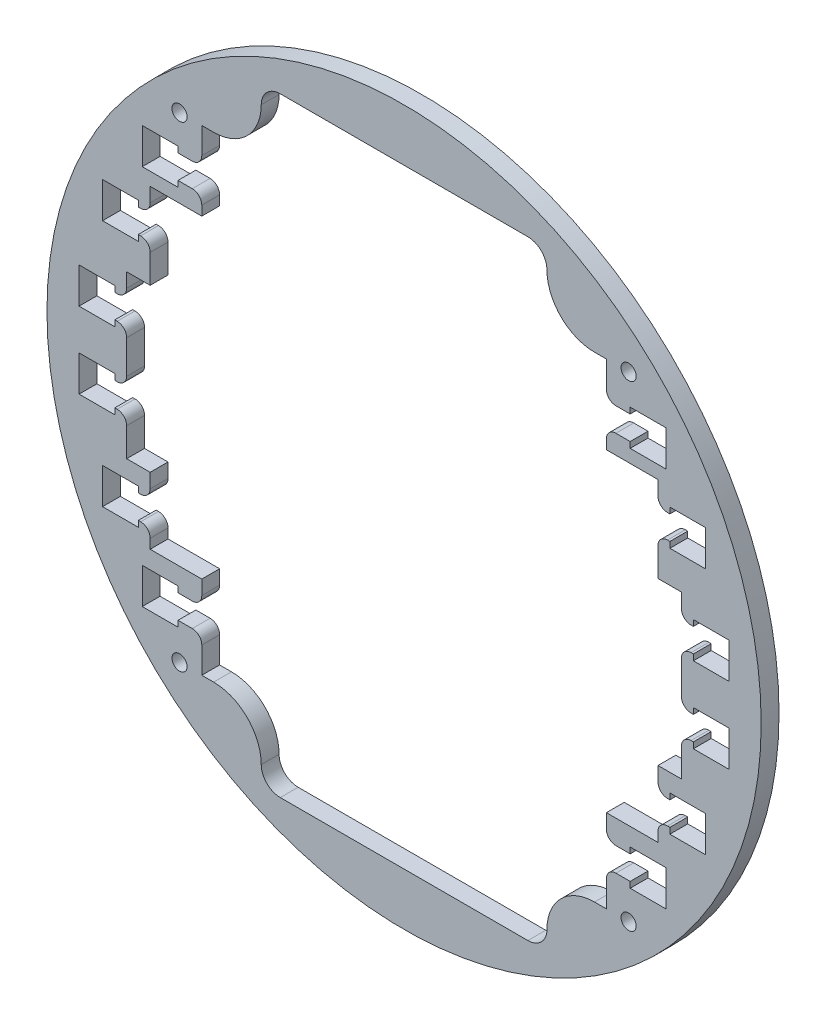
SolidWorks part; units mm, degrees
material "Delrin 2700 NC010, Low Viscosity Acetal Copolymer (SS)"
ref_plane "Front Plane" through (0, 0, 0) normal (0, 0, 1) x (1, 0, 0)
ref_plane "Top Plane" through (0, 0, 0) normal (0, 1, 0) x (1, 0, 0)
ref_plane "Right Plane" through (0, 0, 0) normal (1, 0, 0) x (0, 0, -1)
sketch "Sketch1" plane through (0, 0, 0) normal (0, 0, 1) x (1, 0, 0)
  circle A0 centre (0, 0) radius 95.25
  dimension "D1" = 190.5
extrude "Boss-Extrude1" add sketch "Sketch1" along normal blind 4.7625
sketch "Sketch11" plane through (0, 0, 4.7625) normal (0, 0, 1) x (1, 0, 0)
  line L0 (-69.8306, 55.5625) -> (-69.8306, 46.0375)
  line L1 (-69.8306, 46.0375) -> (-60.3056, 46.0375)
  line L2 (-60.3056, 46.0375) -> (-60.3056, 47.625)
  line L3 (-60.3056, 47.625) -> (-68.2431, 47.625)
  line L4 (-68.2431, 47.625) -> (-68.2431, 53.975)
  line L5 (-68.2431, 53.975) -> (-60.3056, 53.975)
  line L6 (-60.3056, 53.975) -> (-60.3056, 55.5625)
  line L7 (-60.3056, 55.5625) -> (-69.8306, 55.5625)
  line L8 (-69.8306, 50.8) -> (-65.0681, 50.8) construction
  line L9 (-86.6849, 14.9225) -> (-86.6849, 5.3975)
  line L10 (-86.6849, 5.3975) -> (-77.1599, 5.3975)
  line L11 (-77.1599, 5.3975) -> (-77.1599, 6.985)
  line L12 (-77.1599, 6.985) -> (-85.0974, 6.985)
  line L13 (-85.0974, 6.985) -> (-85.0974, 13.335)
  line L14 (-85.0974, 13.335) -> (-77.1599, 13.335)
  line L15 (-77.1599, 13.335) -> (-77.1599, 14.9225)
  line L16 (-77.1599, 14.9225) -> (-86.6849, 14.9225)
  line L17 (-80.4208, 37.7825) -> (-80.4208, 28.2575)
  line L18 (-80.4208, 28.2575) -> (-70.8958, 28.2575)
  line L19 (-70.8958, 28.2575) -> (-70.8958, 29.845)
  line L20 (-70.8958, 29.845) -> (-78.8333, 29.845)
  line L21 (-78.8333, 29.845) -> (-78.8333, 36.195)
  line L22 (-78.8333, 36.195) -> (-70.8958, 36.195)
  line L23 (-70.8958, 36.195) -> (-70.8958, 37.7825)
  line L24 (-70.8958, 37.7825) -> (-80.4208, 37.7825)
  line L25 (-80.4208, 33.02) -> (-75.6583, 33.02) construction
  line L26 (-86.6849, 10.16) -> (-81.9224, 10.16) construction
  line L27 (0, 0) -> (63.3649, 0) construction
  line L28 (-77.1599, -13.335) -> (-77.1599, -14.9225)
  line L29 (-77.1599, -14.9225) -> (-86.6849, -14.9225)
  line L30 (-85.0974, -13.335) -> (-77.1599, -13.335)
  line L31 (-86.6849, -14.9225) -> (-86.6849, -5.3975)
  line L32 (-85.0974, -6.985) -> (-85.0974, -13.335)
  line L33 (-77.1599, -6.985) -> (-85.0974, -6.985)
  line L34 (-77.1599, -5.3975) -> (-77.1599, -6.985)
  line L35 (-86.6849, -5.3975) -> (-77.1599, -5.3975)
  line L36 (-80.4208, -28.2575) -> (-70.8958, -28.2575)
  line L37 (-70.8958, -28.2575) -> (-70.8958, -29.845)
  line L38 (-70.8958, -29.845) -> (-78.8333, -29.845)
  line L39 (-80.4208, -37.7825) -> (-80.4208, -28.2575)
  line L40 (-78.8333, -29.845) -> (-78.8333, -36.195)
  line L41 (-70.8958, -37.7825) -> (-80.4208, -37.7825)
  line L42 (-78.8333, -36.195) -> (-70.8958, -36.195)
  line L43 (-70.8958, -36.195) -> (-70.8958, -37.7825)
  line L44 (-60.3056, -46.0375) -> (-60.3056, -47.625)
  line L45 (-60.3056, -47.625) -> (-68.2431, -47.625)
  line L46 (-69.8306, -46.0375) -> (-60.3056, -46.0375)
  line L47 (-69.8306, -55.5625) -> (-69.8306, -46.0375)
  line L48 (-68.2431, -47.625) -> (-68.2431, -53.975)
  line L49 (-68.2431, -53.975) -> (-60.3056, -53.975)
  line L50 (-60.3056, -55.5625) -> (-69.8306, -55.5625)
  line L51 (-60.3056, -53.975) -> (-60.3056, -55.5625)
  line L52 (0, 0) -> (0, 41.3514) construction
  line L53 (86.6849, 10.16) -> (81.9224, 10.16) construction
  line L54 (80.4208, 33.02) -> (75.6583, 33.02) construction
  line L55 (69.8306, 50.8) -> (65.0681, 50.8) construction
  line L56 (60.3056, -53.975) -> (60.3056, -55.5625)
  line L57 (60.3056, -55.5625) -> (69.8306, -55.5625)
  line L58 (68.2431, -53.975) -> (60.3056, -53.975)
  line L59 (68.2431, -47.625) -> (68.2431, -53.975)
  line L60 (69.8306, -55.5625) -> (69.8306, -46.0375)
  line L61 (69.8306, -46.0375) -> (60.3056, -46.0375)
  line L62 (60.3056, -47.625) -> (68.2431, -47.625)
  line L63 (60.3056, -46.0375) -> (60.3056, -47.625)
  line L64 (70.8958, -36.195) -> (70.8958, -37.7825)
  line L65 (78.8333, -36.195) -> (70.8958, -36.195)
  line L66 (70.8958, -37.7825) -> (80.4208, -37.7825)
  line L67 (78.8333, -29.845) -> (78.8333, -36.195)
  line L68 (80.4208, -37.7825) -> (80.4208, -28.2575)
  line L69 (70.8958, -29.845) -> (78.8333, -29.845)
  line L70 (70.8958, -28.2575) -> (70.8958, -29.845)
  line L71 (80.4208, -28.2575) -> (70.8958, -28.2575)
  line L72 (86.6849, -5.3975) -> (77.1599, -5.3975)
  line L73 (77.1599, -5.3975) -> (77.1599, -6.985)
  line L74 (77.1599, -6.985) -> (85.0974, -6.985)
  line L75 (85.0974, -6.985) -> (85.0974, -13.335)
  line L76 (86.6849, -14.9225) -> (86.6849, -5.3975)
  line L77 (85.0974, -13.335) -> (77.1599, -13.335)
  line L78 (77.1599, -14.9225) -> (86.6849, -14.9225)
  line L79 (77.1599, -13.335) -> (77.1599, -14.9225)
  line L80 (70.8958, 37.7825) -> (80.4208, 37.7825)
  line L81 (70.8958, 36.195) -> (70.8958, 37.7825)
  line L82 (78.8333, 36.195) -> (70.8958, 36.195)
  line L83 (78.8333, 29.845) -> (78.8333, 36.195)
  line L84 (70.8958, 29.845) -> (78.8333, 29.845)
  line L85 (70.8958, 28.2575) -> (70.8958, 29.845)
  line L86 (80.4208, 28.2575) -> (70.8958, 28.2575)
  line L87 (80.4208, 37.7825) -> (80.4208, 28.2575)
  line L88 (77.1599, 14.9225) -> (86.6849, 14.9225)
  line L89 (77.1599, 13.335) -> (77.1599, 14.9225)
  line L90 (85.0974, 13.335) -> (77.1599, 13.335)
  line L91 (85.0974, 6.985) -> (85.0974, 13.335)
  line L92 (77.1599, 6.985) -> (85.0974, 6.985)
  line L93 (77.1599, 5.3975) -> (77.1599, 6.985)
  line L94 (86.6849, 5.3975) -> (77.1599, 5.3975)
  line L95 (86.6849, 14.9225) -> (86.6849, 5.3975)
  line L96 (60.3056, 55.5625) -> (69.8306, 55.5625)
  line L97 (60.3056, 53.975) -> (60.3056, 55.5625)
  line L98 (68.2431, 53.975) -> (60.3056, 53.975)
  line L99 (68.2431, 47.625) -> (68.2431, 53.975)
  line L100 (60.3056, 47.625) -> (68.2431, 47.625)
  line L101 (60.3056, 46.0375) -> (60.3056, 47.625)
  line L102 (69.8306, 46.0375) -> (60.3056, 46.0375)
  line L103 (69.8306, 55.5625) -> (69.8306, 46.0375)
  circle A0 centre (0, 0) radius 82.55 construction
  point P14 (-65.0681, 55.5625)
  point P23 (-81.9224, 14.9225)
  point P32 (-75.6583, 37.7825)
  dimension "D1" = 165.1
  dimension "D2" = 9.525
  dimension "D3" = 9.525
  dimension "D4" = 1.5875
  dimension "D5" = 1.5875
  dimension "D6" = 1.5875
  dimension "D7" = 50.8
  dimension "D8" = 9.525
  dimension "D9" = 9.525
  dimension "D10" = 1.5875
  dimension "D11" = 1.5875
  dimension "D12" = 33.02
  dimension "D13" = 1.5875
  dimension "D14" = 9.525
  dimension "D15" = 9.525
  dimension "D16" = 1.5875
  dimension "D17" = 1.5875
  dimension "D18" = 1.5875
  dimension "D19" = 10.16
extrude "Cut-Extrude1" cut sketch "Sketch11" against normal through all
sketch "Sketch12" plane through (0, 0, 4.7625) normal (0, 0, 1) x (1, 0, 0)
  line L1 (-68.2431, 53.975) -> (68.2431, 53.975)
  line L2 (-68.2431, 53.975) -> (-68.2431, 47.625)
  line L3 (-68.2431, 47.625) -> (68.2431, 47.625)
  line L4 (68.2431, 53.975) -> (68.2431, 47.625)
  line L5 (-78.8333, 36.195) -> (78.8333, 36.195)
  line L6 (-78.8333, 36.195) -> (-78.8333, 29.845)
  line L7 (-78.8333, 29.845) -> (78.8333, 29.845)
  line L8 (78.8333, 36.195) -> (78.8333, 29.845)
  line L9 (-85.0974, 13.335) -> (85.0974, 13.335)
  line L10 (-85.0974, 13.335) -> (-85.0974, 6.985)
  line L11 (-85.0974, 6.985) -> (85.0974, 6.985)
  line L12 (85.0974, 13.335) -> (85.0974, 6.985)
  line L13 (-85.0974, -6.985) -> (85.0974, -6.985)
  line L14 (-85.0974, -6.985) -> (-85.0974, -13.335)
  line L15 (-85.0974, -13.335) -> (85.0974, -13.335)
  line L16 (85.0974, -6.985) -> (85.0974, -13.335)
  line L17 (-78.8333, -29.845) -> (78.8333, -29.845)
  line L18 (-78.8333, -29.845) -> (-78.8333, -36.195)
  line L19 (-78.8333, -36.195) -> (78.8333, -36.195)
  line L20 (78.8333, -29.845) -> (78.8333, -36.195)
  line L21 (-68.2431, -47.625) -> (68.2431, -47.625)
  line L22 (-68.2431, -47.625) -> (-68.2431, -53.975)
  line L23 (-68.2431, -53.975) -> (68.2431, -53.975)
  line L24 (68.2431, -47.625) -> (68.2431, -53.975)
extrude "Cut-Extrude2" cut sketch "Sketch12" against normal through all
sketch "Sketch13" plane through (0, 0, 4.7625) normal (0, 0, 1) x (1, 0, 0)
  line L0 (60.3056, 53.975) -> (-60.3056, 53.975) construction
  line L1 (53.9556, -63.5) -> (-53.9556, -63.5)
  line L2 (53.9556, -63.5) -> (53.9556, -41.275)
  line L3 (53.9556, 63.5) -> (-53.9556, 63.5)
  line L4 (-53.9556, -63.5) -> (-53.9556, -41.275)
  line L5 (53.9556, -63.5) -> (-53.9556, 63.5) construction
  line L6 (53.9556, 63.5) -> (-53.9556, -63.5) construction
  line L7 (-53.9556, 42.545) -> (-67.7208, 42.545)
  line L8 (-67.7208, -23.495) -> (-67.7208, -41.275)
  line L9 (-53.9556, -41.275) -> (-67.7208, -41.275)
  line L10 (-67.7208, 42.545) -> (-67.7208, 19.685)
  line L11 (-67.7208, 19.685) -> (-73.9849, 19.685)
  line L12 (0, 0) -> (0, 113.4572) construction
  line L13 (-67.7208, -23.495) -> (-73.9849, -23.495)
  line L14 (-73.9849, 19.685) -> (-73.9849, -23.495)
  line L15 (-60.3056, 53.975) -> (-60.3056, 55.5625) construction
  line L16 (-70.8958, 36.195) -> (-70.8958, 37.7825) construction
  line L17 (70.8958, 36.195) -> (-70.8958, 36.195) construction
  line L18 (77.1599, 13.335) -> (-77.1599, 13.335) construction
  line L19 (70.8958, -29.845) -> (-70.8958, -29.845) construction
  line L20 (-77.1599, 13.335) -> (-77.1599, 14.9225) construction
  line L21 (60.3056, -47.625) -> (-60.3056, -47.625) construction
  line L22 (-53.9556, 42.545) -> (-53.9556, 63.5)
  line L23 (53.9556, -41.275) -> (67.7208, -41.275)
  line L24 (53.9556, -63.5) -> (53.9556, -41.275)
  line L25 (67.7208, -23.495) -> (67.7208, -41.275)
  line L26 (67.7208, -23.495) -> (73.9849, -23.495)
  line L27 (73.9849, 19.685) -> (73.9849, -23.495)
  line L28 (67.7208, 19.685) -> (73.9849, 19.685)
  line L29 (67.7208, 42.545) -> (67.7208, 19.685)
  line L30 (53.9556, 42.545) -> (67.7208, 42.545)
  line L31 (53.9556, 42.545) -> (53.9556, 63.5)
  line L32 (53.9556, 42.545) -> (53.9556, 63.5)
  point P0 (0, 0)
  dimension "D1" = 9.525
  dimension "D2" = 6.35
  dimension "D3" = 3.175
  dimension "D4" = 6.35
  dimension "D5" = 6.35
  dimension "D6" = 6.35
  dimension "D7" = 3.175
  dimension "D8" = 6.35
extrude "Cut-Extrude3" cut sketch "Sketch13" against normal through all contours L30 L31 L3 L22 L7 L10 L11 L14 L13 L8 L9 L4 L1 L2 L23 L25 L26 L27 L28 L29 region at (0, 0.0263, 4.7625)
hole_wizard "#10-32 Tapped Hole1" positions "Sketch10" profile "Sketch9" tap size "#10-32" standard "ANSI Inch"
sketch "Sketch10" plane through (0, 0, 4.7625) normal (0, 0, 1) x (1, 0, 0)
  line L0 (-59.8919, 63.5) -> (59.8919, 63.5) construction
  point P0 (-59.8919, 63.5)
  point P2 (59.8919, 63.5)
  point P9 (0, 63.5)
  dimension "D1" = 63.5
  dimension "D2" = 119.7837
sketch "Sketch9" plane through (-59.8919, 63.5, 4.7625) normal (1, 0, 0) x (0, -1, 0)
  line L0 (0, 0) -> (0, 11.938)
  line L1 (0, 11.938) -> (2.0193, 11.938)
  line L2 (2.0193, 11.938) -> (2.0193, 0)
  line L5 (2.0193, 0) -> (0, 0)
  line L10 (0, 11.938) -> (-2.0193, 11.938) construction
  line L11 (0, -6.35) -> (0, 107.95) construction
  dimension "Tap Drill Dia." = 4.0386
  dimension "Tap Drill Depth" = 11.938
  dimension "Drill Angle" = 180
cosmetic thread "Hole Thread35" parameters "D1"=4.7625, "D2"=4.826
cosmetic thread "Hole Thread36" parameters "D1"=4.7625, "D2"=4.826
mirror "Mirror1" about plane through (0, 0, 0) normal (0, 1, 0) of "#10-32 Tapped Hole1"
sketch "Sketch14" plane through (0, 0, 4.7625) normal (0, 0, 1) x (1, 0, 0)
  line L1 (38.1, -81.28) -> (-38.1, -81.28)
  line L2 (38.1, -81.28) -> (38.1, 81.28)
  line L3 (38.1, 81.28) -> (-38.1, 81.28)
  line L4 (-38.1, -81.28) -> (-38.1, 81.28)
  line L5 (38.1, -81.28) -> (-38.1, 81.28) construction
  line L6 (38.1, 81.28) -> (-38.1, -81.28) construction
  point P0 (0, 0)
  dimension "D1" = 81.28
  dimension "D2" = 38.1
extrude "Cut-Extrude4" cut sketch "Sketch14" against normal through all
fillet "Fillet1" radius 12.7 4 edges at (38.1, -63.5, 2.3813) (-38.1, -63.5, 2.3813) (38.1, 63.5, 2.3813) (-38.1, 63.5, 2.3813)
fillet "Fillet2" radius 5.08 4 edges at (38.1, -81.28, 2.3813) (-38.1, -81.28, 2.3813) (38.1, 81.28, 2.3813) (-38.1, 81.28, 2.3813)
fillet "Fillet3" radius 2.54 24 edges at (53.9556, 53.975, 2.3813) (53.9556, 47.625, 2.3813) (67.7208, 36.195, 2.3813) (67.7208, 29.845, 2.3813) (73.9849, 13.335, 2.3813) (73.9849, 6.985, 2.3813) (73.9849, -6.985, 2.3813) (73.9849, -13.335, 2.3813) (67.7208, -29.845, 2.3813) (67.7208, -36.195, 2.3813) (53.9556, -47.625, 2.3813) (53.9556, -53.975, 2.3813) (-53.9556, -53.975, 2.3813) (-53.9556, -47.625, 2.3813) (-67.7208, -36.195, 2.3813) (-67.7208, -29.845, 2.3813) (-73.9849, -13.335, 2.3813) (-73.9849, -6.985, 2.3813) (-73.9849, 6.985, 2.3813) (-73.9849, 13.335, 2.3813) (-67.7208, 29.845, 2.3813) (-67.7208, 36.195, 2.3813) (-53.9556, 47.625, 2.3813) (-53.9556, 53.975, 2.3813)
